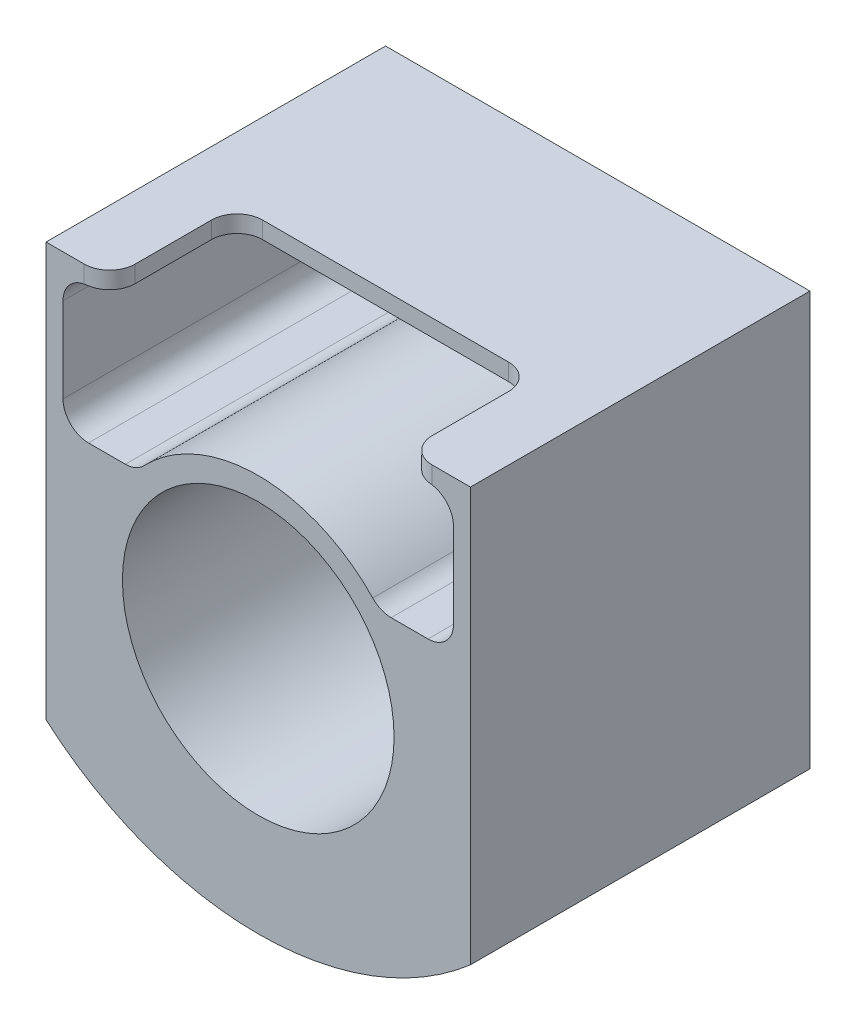
SolidWorks part; units mm, degrees
ref_plane "Front Plane" through (0, 0, 0) normal (0, 0, 1) x (1, 0, 0)
ref_plane "Top Plane" through (0, 0, 0) normal (0, 1, 0) x (1, 0, 0)
ref_plane "Right Plane" through (0, 0, 0) normal (1, 0, 0) x (0, 0, -1)
sketch "Sketch1" plane through (0, 0, 0) normal (0, 0, 1) x (1, 0, 0)
  line L1 (0, 0) -> (0, -38.1) construction
  line L2 (-25, 0) -> (-25, -28.7508)
  line L3 (25, 0) -> (25, -28.7508)
  line L4 (-25, 0) -> (-25, 20)
  line L5 (-25, 20) -> (25, 20)
  line L6 (25, 20) -> (25, 0)
  arc A0 (-25, -28.7508) -> (25, -28.7508) centre (0, 0) ccw
  dimension "D1" = 76.2
  dimension "D2" = 50
  dimension "D3" = 20
extrude "Boss-Extrude2" add sketch "Sketch1" along normal blind 40
sketch "Sketch2" plane through (0, 0, 40) normal (0, 0, 1) x (1, 0, 0)
  line L6 (0, 6) -> (0, -26) construction
  circle A0 centre (0, -10) radius 16
  dimension "D2" = 32
  dimension "D1" = 10
extrude "Cut-Extrude1" cut sketch "Sketch2" against normal through all both
sketch "Sketch4" plane through (0, 0, 40) normal (0, 0, 1) x (1, 0, 0)
  line L0 (-23, 18) -> (23, 18)
  line L3 (0, 20) -> (0, 6) construction
  line L4 (25, 20) -> (-25, 20) construction
  line L5 (23, 2) -> (14.3178, 2)
  line L6 (-23, 18) -> (-23, 2)
  line L7 (-23, 2) -> (-14.3178, 2)
  line L8 (-25, 20) -> (-25, -28.7508) construction
  line L9 (23, 18) -> (23, 2)
  circle A2 centre (0, -10) radius 16 construction
  arc A3 (14.3178, 2) -> (-14.3178, 2) centre (0, -10) ccw
  point P2 (0, 13)
  point P14 (0, 18)
  dimension "D1" = 37.3631
  dimension "D2" = 2
  dimension "D3" = 2
  dimension "D4" = 16
extrude "Cut-Extrude3" cut sketch "Sketch4" against normal through all
fillet "Fillet1" radius 3 6 edges at (23, 18, 20) (23, 2, 20) (14.3178, 2, 20) (-14.3178, 2, 20) (-23, 2, 20) (-23, 18, 20)
sketch "Sketch5" plane through (0, 20, 0) normal (0, 1, 0) x (1, 0, 0)
  line L0 (25, -40) -> (-25, -40) construction
  line L1 (-17.5, -40) -> (17.5, -40)
  line L2 (-17.5, -40) -> (-17.5, -25)
  line L3 (-17.5, -25) -> (17.5, -25)
  line L4 (17.5, -40) -> (17.5, -25)
  line L5 (0, 0) -> (0, -40) construction
  dimension "D1" = 35
  dimension "D2" = 15
extrude "Cut-Extrude4" cut sketch "Sketch5" against normal blind 10
fillet "Fillet2" radius 3 4 edges at (17.5, 19, 40) (17.5, 19, 25) (-17.5, 19, 25) (-17.5, 19, 40)
